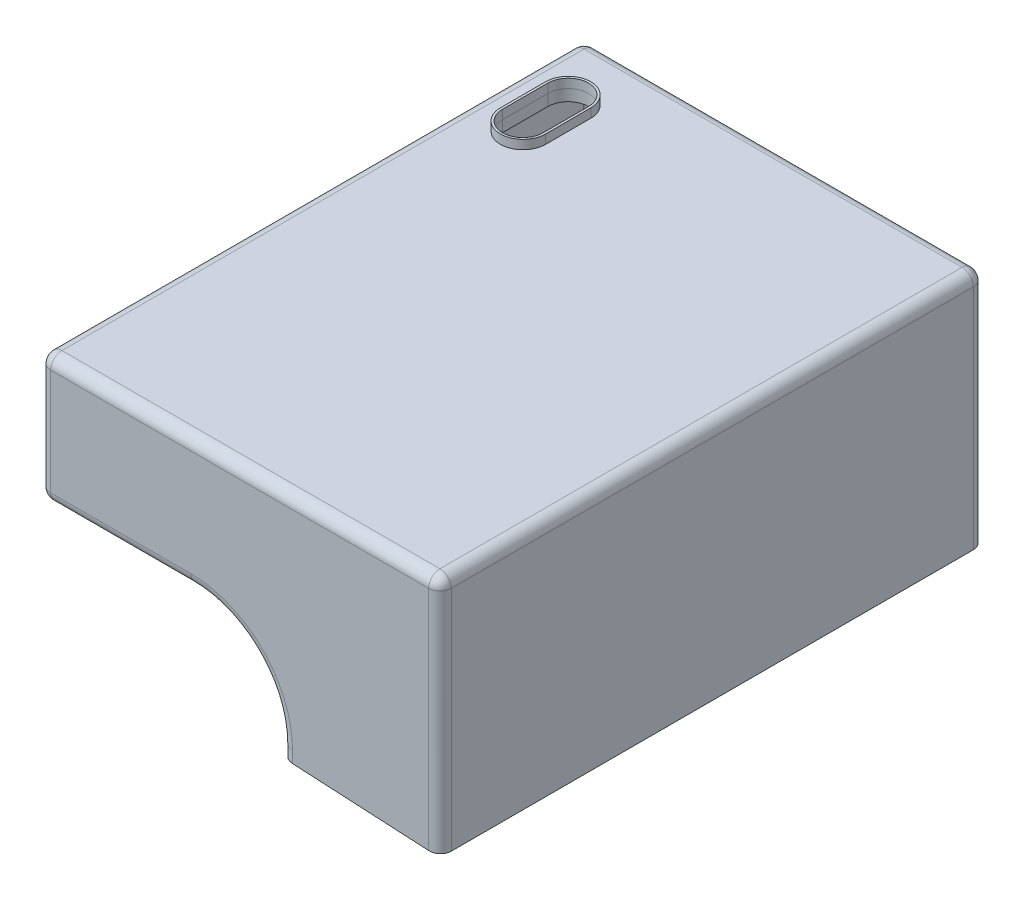
SolidWorks part; units mm, degrees
ref_plane "Plan de face" through (0, 0, 0) normal (0, 0, 1) x (1, 0, 0)
ref_plane "Plan de dessus" through (0, 0, 0) normal (0, 1, 0) x (1, 0, 0)
ref_plane "Plan de droite" through (0, 0, 0) normal (1, 0, 0) x (0, 0, -1)
sketch "Esquisse1" plane through (0, 0, 0) normal (0, 0, 1) x (1, 0, 0)
  line L0 (5, 0) -> (67, 0)
  line L1 (107, -40) -> (107, -45)
  line L7 (0, 52) -> (0, 5)
  line L11 (5, 57) -> (172.2575, 57)
  line L15 (177.2575, 52) -> (177.2575, -48.7435)
  line L16 (177.2575, -48.7435) -> (107, -45)
  arc A0 (67, 0) -> (107, -40) centre (67, -40) cw
  arc A2 (5, 0) -> (0, 5) centre (5, 5) cw
  arc A3 (5, 57) -> (0, 52) centre (5, 52) ccw
  arc A4 (177.2575, 52) -> (172.2575, 57) centre (172.2575, 52) ccw
  point P3 (0, 0)
  point P7 (0, 0)
  point P8 (179.7628, 55.3371)
  point P11 (107, 0)
  point P17 (0, 0)
  dimension "D7" = 40
  dimension "D9" = 5
  dimension "D4" = 177.2575
  dimension "D5" = 5
  dimension "D1" = 57
  dimension "D2" = 86.95
  dimension "D3" = 45
  dimension "D6" = 107
extrude "Boss.-Extru.1" add sketch "Esquisse1" along normal blind 241
fillet "Congé1" radius 5 16 edges at (107, -42.5, 0) (95.2843, -11.7157, 0) (36, 0, 0) (1.4645, 1.4645, 0) (0, 28.5, 0) (1.4645, 55.5355, 0) (88.6288, 57, 0) (107, -42.5, 241) (95.2843, -11.7157, 241) (36, 0, 241) (1.4645, 1.4645, 241) (0, 28.5, 241) (1.4645, 55.5355, 241) (88.6288, 57, 241) (177.2575, 1.6282, 0) (177.2575, 1.6282, 241) tangent propagation no
sketch "Esquisse3" plane through (0, 57, 0) normal (0, 1, 0) x (1, 0, 0)
  line L0 (13, -30) -> (13, -50)
  line L2 (33, -50) -> (33, -30)
  line L5 (0, -236) -> (0, -5) construction
  line L6 (5, 0) -> (172.2575, 0) construction
  arc A1 (13, -30) -> (33, -30) centre (23, -30) cw
  arc A2 (33, -50) -> (13, -50) centre (23, -50) cw
  dimension "D1" = 13
  dimension "D2" = 30
  dimension "D3" = 20
extrude "Boss.-Extru.2" add sketch "Esquisse3" along normal blind 4 separate body
sketch "Esquisse5" plane through (0, 61, 0) normal (0, 1, 0) x (1, 0, 0)
  line L0 (14.0023, -30) -> (14.0023, -50.0889)
  line L2 (32, -50.0889) -> (32, -30)
  line L4 (13, -30) -> (13, -50) construction
  line L5 (33, -50) -> (33, -30) construction
  arc A0 (14.0023, -30) -> (32, -30) centre (23.0011, -30) cw
  arc A1 (32, -50.0889) -> (14.0023, -50.0889) centre (23.0011, -50.0889) cw
  dimension "D1" = 1.0023
  dimension "D2" = 1
extrude "Enlèv. mat.-Extru.2" cut sketch "Esquisse5" against normal blind 9
shell "Coque1" thickness 5 removed face at (23.0011, 52, 40.0444)
